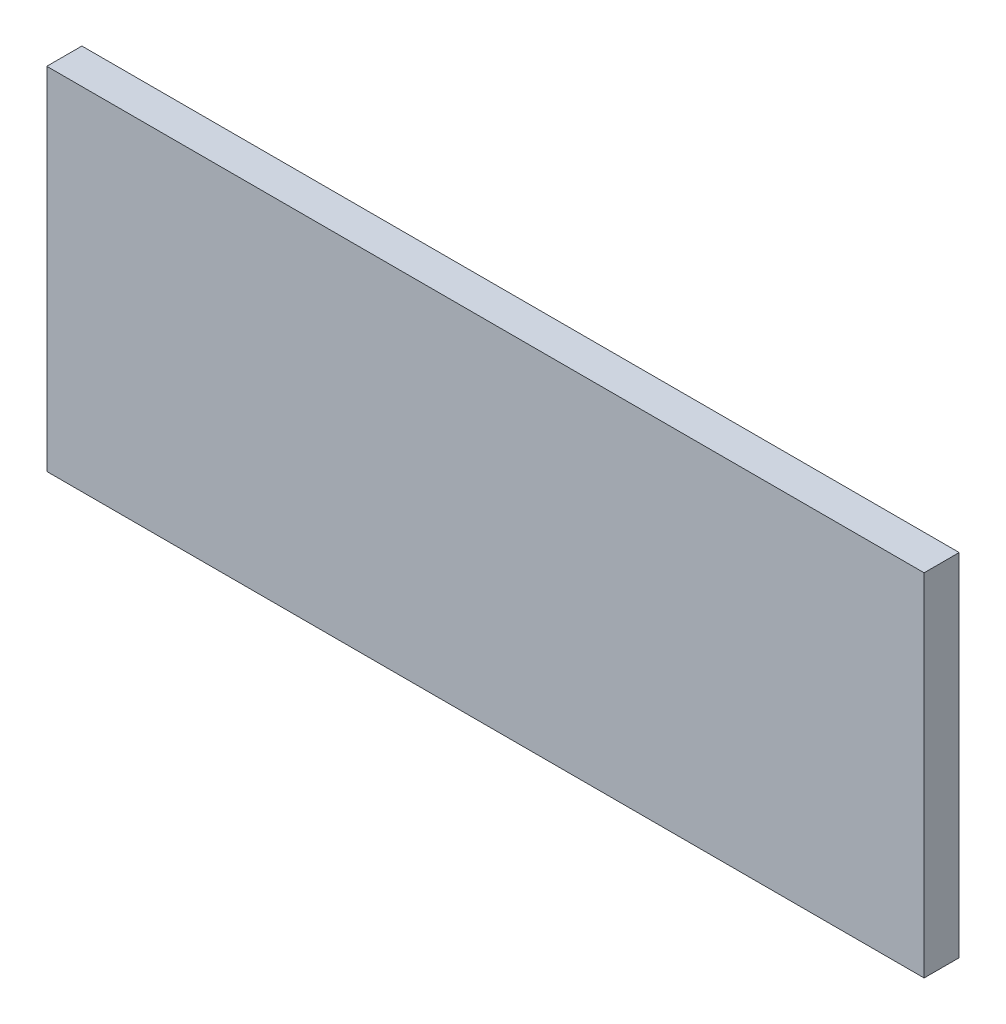
SolidWorks part; units mm, degrees
material "Лист 4,0 ГОСТ 19903-2015 / Ст3сп ГОСТ 14637-89"
ref_plane "Спереди" through (0, 0, 0) normal (0, 0, 1) x (1, 0, 0)
ref_plane "Сверху" through (0, 0, 0) normal (0, 1, 0) x (1, 0, 0)
ref_plane "Справа" through (0, 0, 0) normal (1, 0, 0) x (0, 0, -1)
sketch "Эскиз1" plane through (0, 0, 0) normal (0, 0, 1) x (1, 0, 0)
  line L1 (-50, -20) -> (50, -20)
  line L2 (-50, -20) -> (-50, 20)
  line L3 (-50, 20) -> (50, 20)
  line L4 (50, -20) -> (50, 20)
base flange "Базовая кромка1" sketch "Эскиз1" thickness 4 reverse thickness direction no parameters "D1"=4
sketch "Эскиз6" plane through (0, 0, 0) normal (0, 0, 1) x (1, 0, 0)
  line L1 (50, -20) -> (100, -20)
  line L2 (50, -20) -> (50, 20)
  line L3 (50, 20) -> (100, 20)
  line L4 (100, -20) -> (100, 20)
base flange "Выступ1" [suppressed] sketch "Эскиз6" thickness 4 reverse thickness direction no parameters "D1"=4
sketch "Эскиз9" plane through (0, 0, 0) normal (0, 0, 1) x (1, 0, 0)
  line L1 (100, -20) -> (150, -20)
  line L2 (100, -20) -> (100, 20)
  line L3 (100, 20) -> (150, 20)
  line L4 (150, -20) -> (150, 20)
base flange "Выступ2" [suppressed] sketch "Эскиз9" thickness 4 reverse thickness direction no parameters "D1"=4
sketch "Сгиб-Линии1" [suppressed] plane through (0, 0, 0) normal (0, 1, 0) x (1, 0, 0)
sketch "Граничная рамка1" [suppressed] plane through (0, 0, 0) normal (0, 1, 0) x (1, 0, 0)
sheet metal parameters "Листовой металл32" thickness 4 parameters "D1"=4
flat pattern "Развертка32" [suppressed]
sketch "Сгиб-Линии2" plane through (0, 0, 0) normal (0, 1, 0) x (1, 0, 0)
sketch3d "Граничная рамка2" [suppressed]
  line L0 (50, -20, 0) -> (-50, -20, 0) construction
  line L1 (50, 20, 0) -> (-50, 20, 0) construction
  line L2 (50, -20, 0) -> (50, 20, 0) construction
  line L3 (-50, -20, 0) -> (-50, 20, 0) construction
sheet metal parameters "Листовой металл33" thickness 4 parameters "D1"=4
flat pattern "Развертка33"
sketch "Сгиб-Линии3" plane through (0, 0, 0) normal (0, 1, 0) x (1, 0, 0)
sketch3d "Граничная рамка3" [suppressed]
  line L0 (50, -20, 0) -> (-100, -20, 0) construction
  line L1 (50, 20, 0) -> (-100, 20, 0) construction
  line L2 (50, -20, 0) -> (50, 20, 0) construction
  line L3 (-100, -20, 0) -> (-100, 20, 0) construction
sheet metal parameters "Листовой металл34" thickness 4 parameters "D1"=4
flat pattern "Развертка34"
sketch "Сгиб-Линии4" plane through (0, 0, 0) normal (0, 1, 0) x (1, 0, 0)
sketch3d "Граничная рамка4" [suppressed]
  line L0 (50, -20, 0) -> (-150, -20, 0) construction
  line L1 (50, 20, 0) -> (-150, 20, 0) construction
  line L2 (50, -20, 0) -> (50, 20, 0) construction
  line L3 (-150, -20, 0) -> (-150, 20, 0) construction
